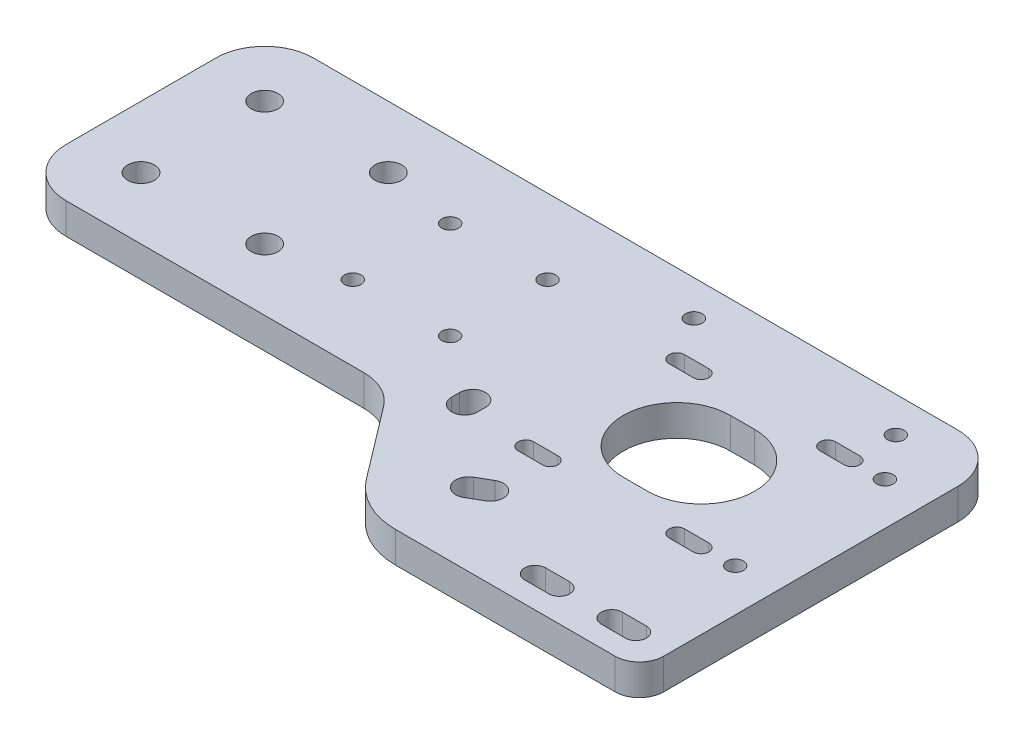
SolidWorks part; units mm, degrees
ref_plane "Front" through (0, 0, 0) normal (0, 0, 1) x (1, 0, 0)
ref_plane "Top" through (0, 0, 0) normal (0, 1, 0) x (1, 0, 0)
ref_plane "Right" through (0, 0, 0) normal (1, 0, 0) x (0, 0, -1)
sketch "Sketch1" plane through (0, 0, 0) normal (0, 1, 0) x (1, 0, 0)
  line L0 (0, 0) -> (114.3212, 0) construction
  line L1 (38.1, -25.4) -> (-38.1, -25.4)
  line L2 (38.1, -25.4) -> (38.1, 25.4) construction
  line L3 (38.1, 25.4) -> (-38.1, 25.4)
  line L4 (-38.1, -25.4) -> (-38.1, 25.4)
  line L5 (38.1, -25.4) -> (-38.1, 25.4) construction
  line L6 (38.1, 25.4) -> (-38.1, -25.4) construction
  line L7 (25.4, 25.4) -> (25.4, -25.4) construction
  line L8 (-25.4, 25.4) -> (-25.4, -25.4) construction
  line L9 (0, -25.4) -> (0, 25.4) construction
  line L10 (0, 0) -> (-38.1, 0) construction
  line L11 (-25.4, 0) -> (-25.4, 25.4) construction
  line L12 (-25.4, 12.7) -> (0, 12.7) construction
  line L13 (25.4, -41.4) -> (114.3212, -41.4) construction
  line L14 (99.3212, -27.36) -> (57.3212, -27.36) construction
  line L15 (99.3212, -27.36) -> (99.3212, 14.64) construction
  line L16 (99.3212, 14.64) -> (57.3212, 14.64) construction
  line L17 (57.3212, -27.36) -> (57.3212, 14.64) construction
  line L18 (99.3212, -27.36) -> (57.3212, 14.64) construction
  line L19 (99.3212, 14.64) -> (57.3212, -27.36) construction
  line L20 (93.8212, -21.86) -> (62.8212, -21.86) construction
  line L21 (93.8212, -21.86) -> (93.8212, 9.14) construction
  line L22 (93.8212, 9.14) -> (62.8212, 9.14) construction
  line L23 (62.8212, -21.86) -> (62.8212, 9.14) construction
  line L24 (93.8212, -21.86) -> (62.8212, 9.14) construction
  line L25 (93.8212, 9.14) -> (62.8212, -21.86) construction
  line L26 (114.3212, -41.4) -> (114.3212, 0) construction
  line L27 (49.1, -12.72) -> (78.3212, -12.72) construction
  line L28 (47.8664, -25.3192) -> (65.4755, -28.8008) construction
  line L29 (38.1, -25.4) -> (52.2919, -44.1062)
  line L30 (78.3212, 0) -> (0, 0) construction
  line L31 (35.4, 10) -> (15.4, 10) construction
  line L32 (64.2419, -50.04) -> (114.3212, -50.04)
  line L33 (114.3212, -50.04) -> (114.3212, 25.4)
  line L34 (114.3212, 25.4) -> (38.1, 25.4)
  line L35 (49.1, -19.08) -> (49.1, -20.72) construction
  line L36 (64.2419, -35.04) -> (67.0783, -33.4) construction
  line L37 (64.2419, -35.04) -> (64.2419, -50.04) construction
  circle A0 centre (-25.4, 12.7) radius 2.5 construction
  circle A1 centre (0, 12.7) radius 2.5 construction
  circle A2 centre (-25.4, -12.7) radius 2.5 construction
  circle A3 centre (0, -12.7) radius 2.5 construction
  circle A4 centre (78.3212, -6.36) radius 6.36 construction
  circle A5 centre (78.3212, -6.36) radius 11 construction
  circle A6 centre (62.8212, 9.14) radius 1.5 construction
  circle A7 centre (93.8212, 9.14) radius 1.5 construction
  circle A8 centre (93.8212, -21.86) radius 1.5 construction
  circle A9 centre (62.8212, -21.86) radius 1.5 construction
  circle A10 centre (64.2419, -35.04) radius 6.36 construction
  circle A11 centre (64.2419, -35.04) radius 11 construction
  circle A12 centre (49.1, -19.08) radius 6.36 construction
  circle A13 centre (49.1, -19.08) radius 11 construction
  circle A14 centre (62.8212, -21.86) radius 3 construction
  circle A15 centre (35.4, 10) radius 1.5 construction
  circle A16 centre (15.4, 10) radius 1.5 construction
  circle A17 centre (35.4, -10) radius 1.5 construction
  circle A18 centre (15.4, -10) radius 1.5 construction
  circle A19 centre (49.1, -19.08) radius 2.5 construction
  circle A20 centre (64.2419, -35.04) radius 2.5 construction
  circle A21 centre (78.3212, -6.36) radius 11 construction
  arc A22 (52.2919, -44.1062) -> (64.2419, -50.04) centre (64.2419, -35.04) ccw
  circle A23 centre (49.1, -20.72) radius 8 construction
  circle A24 centre (49.1, -20.72) radius 11 construction
  circle A25 centre (67.0783, -33.4) radius 8 construction
  circle A26 centre (67.0783, -33.4) radius 11 construction
  point P0 (0, 0)
  point P54 (25.4, 10)
  dimension "D6" = 5
  dimension "D7" = 12.72
  dimension "D9" = 22
  dimension "D11" = 3
  dimension "D12" = 16
  dimension "D13" = 6
  dimension "D16" = 3
  dimension "D17" = 5
  dimension "D18" = 22
  dimension "D20" = 16
  dimension "D21" = 4
  dimension "D1" = 50.8
  dimension "D2" = 76.2
  dimension "D3" = 12.7
  dimension "D4" = 12.7
  dimension "D5" = 25.4
  dimension "D8" = 42
  dimension "D10" = 31
  dimension "D14" = 20
  dimension "D15" = 10
  dimension "D19" = 15
extrude "Boss-Extrude1" add sketch "Sketch1" along normal blind 6.35
hole_wizard "M5 Clearance Hole1" positions "Sketch3" profile "Sketch2" hole size "M5" standard "ISO" end condition through all
sketch "Sketch3" plane through (0, 6.35, 0) normal (0, 1, 0) x (1, 0, 0)
  point P0 (-25.4, 12.7)
  point P3 (0, 12.7)
  point P6 (0, -12.7)
  point P9 (-25.4, -12.7)
sketch "Sketch2" plane through (-25.4, 6.35, -12.7) normal (1, 0, 0) x (0, 0, 1)
  line L0 (0, 0) -> (0, 6.35)
  line L1 (0, 6.35) -> (2.75, 6.35)
  line L2 (2.75, 6.35) -> (2.75, 0)
  line L5 (2.75, 0) -> (0, 0)
  line L11 (0, -6.35) -> (0, 107.95) construction
  dimension "Thru Hole Dia." = 5.5
  dimension "Thru Hole Depth" = 6.35
hole_wizard "M3 Clearance Hole1" positions "Sketch5" profile "Sketch4" hole size "M3" standard "ISO" end condition through all
sketch "Sketch5" plane through (0, 6.35, 0) normal (0, 1, 0) x (1, 0, 0)
  point P0 (15.4, 10)
  point P3 (35.4, 10)
  point P6 (35.4, -10)
  point P9 (15.4, -10)
sketch "Sketch4" plane through (15.4, 6.35, -10) normal (1, 0, 0) x (0, 0, 1)
  line L0 (0, 0) -> (0, 6.35)
  line L1 (0, 6.35) -> (1.7, 6.35)
  line L2 (1.7, 6.35) -> (1.7, 0)
  line L5 (1.7, 0) -> (0, 0)
  line L11 (0, -6.35) -> (0, 107.95) construction
  dimension "Thru Hole Dia." = 3.4
  dimension "Thru Hole Depth" = 6.35
sketch "Sketch6" plane through (0, 6.35, 0) normal (0, 1, 0) x (1, 0, 0)
  line L0 (62.8212, 9.14) -> (67.8212, 9.14) construction
  line L1 (93.8212, 9.14) -> (62.8212, 9.14) construction
  line L2 (62.8212, -21.86) -> (67.8212, -21.86) construction
  line L3 (93.8212, -21.86) -> (62.8212, -21.86) construction
  line L4 (93.8212, -21.86) -> (98.8212, -21.86) construction
  line L5 (93.8212, 9.14) -> (98.8212, 9.14) construction
  line L6 (62.8212, 7.54) -> (67.8212, 7.54)
  line L7 (62.8212, -23.46) -> (67.8212, -23.46)
  line L8 (93.8212, -23.46) -> (98.8212, -23.46)
  line L9 (93.8212, 7.54) -> (98.8212, 7.54)
  line L10 (62.8212, 10.74) -> (67.8212, 10.74)
  line L11 (62.8212, -20.26) -> (67.8212, -20.26)
  line L12 (93.8212, -20.26) -> (98.8212, -20.26)
  line L13 (93.8212, 10.74) -> (98.8212, 10.74)
  line L14 (78.3212, -6.36) -> (83.3212, -6.36) construction
  line L15 (99.3212, 14.64) -> (57.3212, -27.36) construction
  line L16 (78.3212, -17.36) -> (83.3212, -17.36)
  line L17 (78.3212, 4.64) -> (83.3212, 4.64)
  arc A0 (62.8212, 7.54) -> (62.8212, 10.74) centre (62.8212, 9.14) cw
  arc A1 (67.8212, 7.54) -> (67.8212, 10.74) centre (67.8212, 9.14) ccw
  arc A2 (62.8212, -23.46) -> (62.8212, -20.26) centre (62.8212, -21.86) cw
  arc A3 (67.8212, -23.46) -> (67.8212, -20.26) centre (67.8212, -21.86) ccw
  arc A4 (93.8212, -23.46) -> (93.8212, -20.26) centre (93.8212, -21.86) cw
  arc A5 (98.8212, -23.46) -> (98.8212, -20.26) centre (98.8212, -21.86) ccw
  arc A6 (93.8212, 7.54) -> (93.8212, 10.74) centre (93.8212, 9.14) cw
  arc A7 (98.8212, 7.54) -> (98.8212, 10.74) centre (98.8212, 9.14) ccw
  arc A8 (78.3212, -17.36) -> (78.3212, 4.64) centre (78.3212, -6.36) cw
  arc A9 (83.3212, -17.36) -> (83.3212, 4.64) centre (83.3212, -6.36) ccw
  dimension "D1" = 5
  dimension "D2" = 1.6
  dimension "D3" = 1.6
  dimension "D4" = 11
  dimension "D5" = 11
extrude "Cut-Extrude1" cut sketch "Sketch6" against normal through all
sketch "Sketch7" plane through (0, 6.35, 0) normal (0, 1, 0) x (1, 0, 0)
  line L0 (49.1, -19.08) -> (49.1, -20.72) construction
  line L1 (67.0783, -33.4) -> (64.2419, -35.04) construction
  line L2 (65.7518, -31.1059) -> (62.9155, -32.7459)
  line L3 (46.45, -19.08) -> (46.45, -20.72)
  line L4 (68.4047, -35.6941) -> (65.5684, -37.3341)
  line L5 (51.75, -19.08) -> (51.75, -20.72)
  arc A0 (65.7518, -31.1059) -> (68.4047, -35.6941) centre (67.0783, -33.4) cw
  arc A1 (62.9155, -32.7459) -> (65.5684, -37.3341) centre (64.2419, -35.04) ccw
  arc A2 (46.45, -19.08) -> (51.75, -19.08) centre (49.1, -19.08) cw
  arc A3 (46.45, -20.72) -> (51.75, -20.72) centre (49.1, -20.72) ccw
  dimension "D1" = 2.65
  dimension "D2" = 2.65
extrude "Cut-Extrude2" cut sketch "Sketch7" against normal through all
fillet "Fillet1" radius 10 4 edges at (114.3212, 3.175, -25.4) (38.1, 3.175, 25.4) (-38.1, 3.175, -25.4) (-38.1, 3.175, 25.4)
sketch "Sketch8" plane through (0, 6.35, 0) normal (0, 1, 0) x (1, 0, 0)
  line L0 (114.3212, -43.61) -> (79.3212, -43.61) construction
  line L1 (114.3212, -50.04) -> (114.3212, 15.4) construction
  line L2 (89.0712, -43.61) -> (104.5712, -43.61) construction
  line L3 (96.8212, -43.61) -> (96.8212, -25.11) construction
  line L4 (114.3212, -25.11) -> (79.3212, -25.11) construction
  line L5 (79.3212, -25.11) -> (79.3212, -57.11) construction
  line L6 (79.3212, -57.11) -> (114.3212, -57.11) construction
  line L7 (114.3212, -57.11) -> (114.3212, -25.11) construction
  line L8 (107.1712, -41.46) -> (102.2212, -41.46)
  line L9 (86.4712, -43.61) -> (91.4212, -43.61) construction
  line L10 (86.4712, -45.76) -> (91.4212, -45.76)
  line L11 (86.4712, -41.46) -> (91.4212, -41.46)
  line L12 (84.3212, -43.61) -> (84.3212, -50.04) construction
  line L13 (64.2419, -50.04) -> (114.3212, -50.04) construction
  line L14 (93.5712, -43.61) -> (93.5712, -50.04) construction
  line L15 (107.1712, -45.76) -> (102.2212, -45.76)
  circle A0 centre (104.5712, -43.61) radius 2 construction
  circle A1 centre (89.0712, -43.61) radius 2 construction
  arc A2 (86.4712, -45.76) -> (86.4712, -41.46) centre (86.4712, -43.61) cw
  arc A3 (91.4212, -45.76) -> (91.4212, -41.46) centre (91.4212, -43.61) ccw
  circle A4 centre (93.8212, -21.86) radius 3.25 construction
  circle A5 centre (67.0783, -33.4) radius 11 construction
  arc A6 (107.1712, -41.46) -> (107.1712, -45.76) centre (107.1712, -43.61) cw
  arc A7 (102.2212, -41.46) -> (102.2212, -45.76) centre (102.2212, -43.61) ccw
  point P13 (96.8212, -25.11)
  dimension "D3" = 4
  dimension "D11" = 6.5
  dimension "D12" = 22
  dimension "D2" = 15.5
  dimension "D4" = 18.5
  dimension "D5" = 32
  dimension "D8" = 25
  dimension "D9" = 6.5
  dimension "D10" = 35
  dimension "D6" = 2.15
  dimension "D7" = 2.15
extrude "Cut-Extrude3" cut sketch "Sketch8" against normal through all
sketch "Sketch10" plane through (0, 6.35, 0) normal (0, 1, 0) x (1, 0, 0)
  line L0 (114.3212, -25.11) -> (79.3212, -25.11) construction
  line L1 (57.3212, 14.64) -> (57.3212, 18.14) construction
  line L2 (57.3212, 18.14) -> (98.8212, 18.14) construction
  line L3 (98.8212, 18.14) -> (98.8212, 9.14) construction
  line L4 (98.8212, 9.14) -> (105.5666, 9.14) construction
  line L5 (105.5666, 9.14) -> (105.5666, -21.61) construction
  line L7 (99.3212, 14.64) -> (57.3212, 14.64) construction
  circle A0 centre (105.5666, -21.61) radius 3.5
  circle A1 centre (98.8212, -21.86) radius 3.25 construction
  circle A2 centre (98.8212, 9.14) radius 3.25 construction
  circle A3 centre (105.5666, 9.14) radius 3.5
  circle A4 centre (98.8212, 18.14) radius 3.5
  circle A5 centre (57.3212, 18.14) radius 3.5
  dimension "D1" = 6.5
  dimension "D2" = 7
hole_wizard "M3 Clearance Hole2" positions "Sketch12" profile "Sketch11" hole size "M3" standard "ISO" end condition through all
sketch "Sketch12" plane through (0, 6.35, 0) normal (0, 1, 0) x (1, 0, 0)
  point P0 (57.3212, 18.14)
  point P3 (98.8212, 18.14)
  point P6 (105.5666, 9.14)
  point P9 (105.5666, -21.61)
sketch "Sketch11" plane through (57.3212, 6.35, -18.14) normal (1, 0, 0) x (0, 0, 1)
  line L0 (0, 0) -> (0, 6.35)
  line L1 (0, 6.35) -> (1.7, 6.35)
  line L2 (1.7, 6.35) -> (1.7, 0)
  line L5 (1.7, 0) -> (0, 0)
  line L11 (0, -6.35) -> (0, 107.95) construction
  dimension "Thru Hole Dia." = 3.4
  dimension "Thru Hole Depth" = 6.35
fillet "Fillet3" radius 5 1 edges at (114.3212, 3.175, 50.04)
